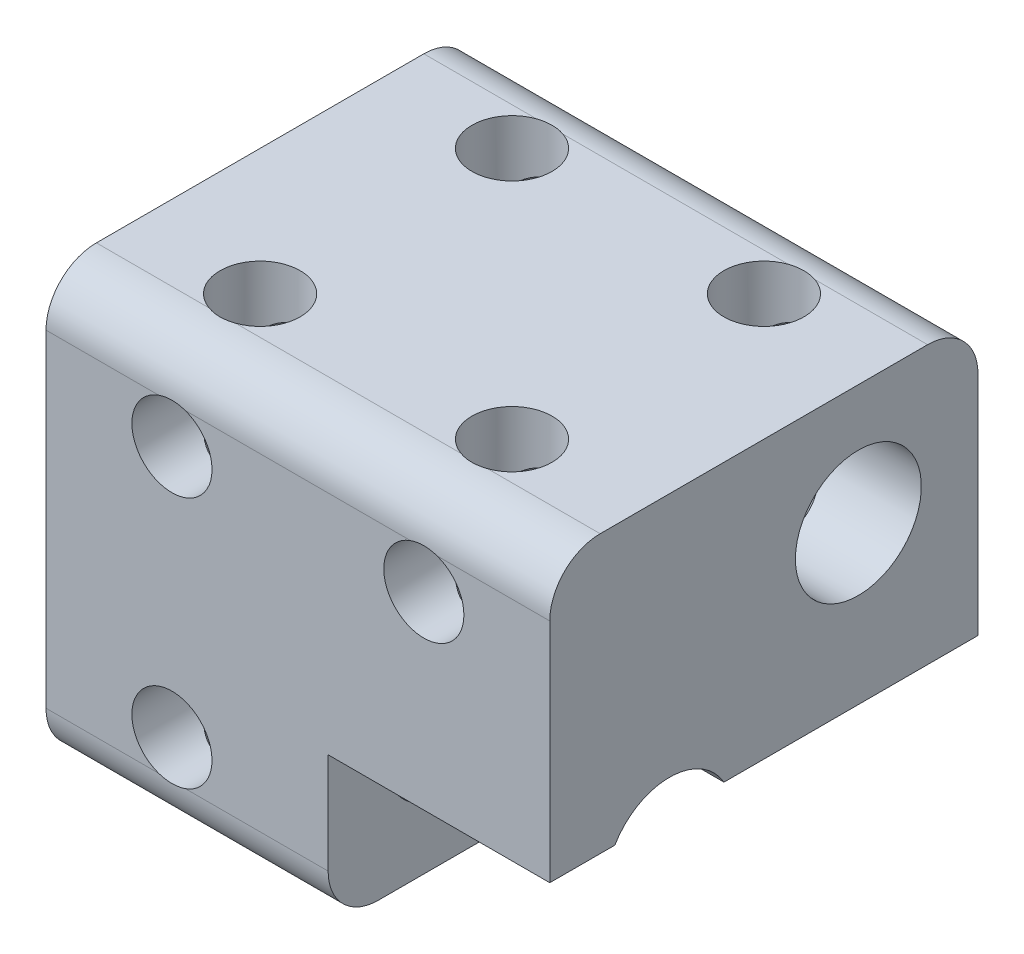
SolidWorks part; units mm, degrees
material "PET"
ref_plane "Front" through (0, 0, 0) normal (0, 0, 1) x (1, 0, 0)
ref_plane "Top" through (0, 0, 0) normal (0, 1, 0) x (1, 0, 0)
ref_plane "Right" through (0, 0, 0) normal (1, 0, 0) x (0, 0, -1)
sketch "Sketch1" plane through (0, 0, 0) normal (1, 0, 0) x (0, 0, -1)
  line L1 (8.255, -10.795) -> (-8.255, -10.795)
  line L2 (10.795, -8.255) -> (10.795, 8.255)
  line L3 (8.255, 10.795) -> (-8.255, 10.795)
  line L4 (-10.795, -8.255) -> (-10.795, 8.255)
  line L5 (10.795, -10.795) -> (-10.795, 10.795) construction
  line L6 (10.795, 10.795) -> (-10.795, -10.795) construction
  arc A0 (10.795, 8.255) -> (8.255, 10.795) centre (8.255, 8.255) ccw
  arc A1 (8.255, -10.795) -> (10.795, -8.255) centre (8.255, -8.255) ccw
  arc A2 (-8.255, -10.795) -> (-10.795, -8.255) centre (-8.255, -8.255) cw
  arc A3 (-8.255, 10.795) -> (-10.795, 8.255) centre (-8.255, 8.255) ccw
  point P0 (0, 0)
  dimension "D2" = 2.54
  dimension "D1" = 21.59
extrude "Boss-Extrude1" add sketch "Sketch1" along normal blind 25.4
sketch "Sketch4" plane through (0, 0, 0) normal (-1, 0, 0) x (0, 0, 1)
  line L0 (-4.7625, 4.7625) -> (4.7625, -4.7625) construction
  point P0 (-4.7625, 4.7625)
  point P2 (4.7625, -4.7625)
  dimension "D1" = 9.525
  dimension "D2" = 9.525
hole_wizard "1/4 (0.2500) Dowel Hole1" positions "Sketch4" profile "Sketch3" hole size "1/4" standard "ANSI Inch" end condition through all
sketch "Sketch3" plane through (0, 4.7625, -4.7625) normal (0, 1, 0) x (0, 0, 1)
  line L0 (0, 0) -> (0, 25.4)
  line L1 (0, 25.4) -> (3.175, 25.4)
  line L2 (3.175, 25.4) -> (3.175, 0)
  line L5 (3.175, 0) -> (0, 0)
  line L11 (0, -6.35) -> (0, 107.95) construction
  dimension "Thru Hole Dia." = 6.35
  dimension "Thru Hole Depth" = 25.4
sketch "Sketch7" plane through (0, 0, 10.795) normal (0, 0, 1) x (1, 0, 0)
  line L0 (0, -10.795) -> (6.35, -6.35) construction
  line L3 (0, 10.795) -> (6.35, 6.35) construction
  line L4 (0, 10.795) -> (0, 8.255) construction
  point P0 (6.35, 6.35)
  point P2 (19.05, 6.35)
  point P5 (6.35, -6.35)
  point P7 (19.05, -6.35)
  dimension "D1" = 12.7
  dimension "D2" = 12.7
  dimension "D3" = 6.35
hole_wizard "#10-32 Tapped Hole2" positions "Sketch7" profile "Sketch6" tap size "#10-32" standard "ANSI Inch" end condition through all
sketch "Sketch6" plane through (6.35, 6.35, 10.795) normal (1, 0, 0) x (0, -1, 0)
  line L0 (0, 0) -> (0, 21.59)
  line L1 (0, 21.59) -> (2.0193, 21.59)
  line L2 (2.0193, 21.59) -> (2.0193, 0)
  line L5 (2.0193, 0) -> (0, 0)
  line L11 (0, -6.35) -> (0, 107.95) construction
  dimension "Thru Tap Drill Dia." = 4.0386
  dimension "Thru Tap Drill Depth" = 21.59
cosmetic thread "Hole Thread3" parameters "D2"=4.826
cosmetic thread "Hole Thread4" parameters "D2"=4.826
cosmetic thread "Hole Thread5" parameters "D2"=4.826
cosmetic thread "Hole Thread6" parameters "D2"=4.826
ref_plane "Plane1" through (0, 0, 0) normal (0, -0.7071, 0.7071) x (1, 0, 0)
mirror "Mirror1" about plane through (0, 0, 0) normal (0, -0.7071, 0.7071) of "#10-32 Tapped Hole2"
cosmetic thread "Hole Thread7" parameters "D2"=4.826
cosmetic thread "Hole Thread8" parameters "D2"=4.826
cosmetic thread "Hole Thread9" parameters "D2"=4.826
cosmetic thread "Hole Thread10" parameters "D2"=4.826
sketch "Sketch8" plane through (25.4, 0, 0) normal (1, 0, 0) x (0, 0, -1)
  line L0 (-10.795, 8.255) -> (-10.795, -8.255) construction
  line L1 (-10.795, -3.175) -> (10.795, -3.175)
  line L2 (-10.795, -3.175) -> (-10.795, -10.795)
  line L3 (-10.795, -10.795) -> (10.795, -10.795)
  line L4 (10.795, -3.175) -> (10.795, -10.795)
  line L5 (-8.255, -10.795) -> (8.255, -10.795) construction
  line L6 (10.795, -8.255) -> (10.795, 8.255) construction
  dimension "D1" = 7.62
extrude "Cut-Extrude1" cut sketch "Sketch8" against normal offset from surface (11.176 mm away) 14.224 up to face at (0, 4.7625, -1.5875)
